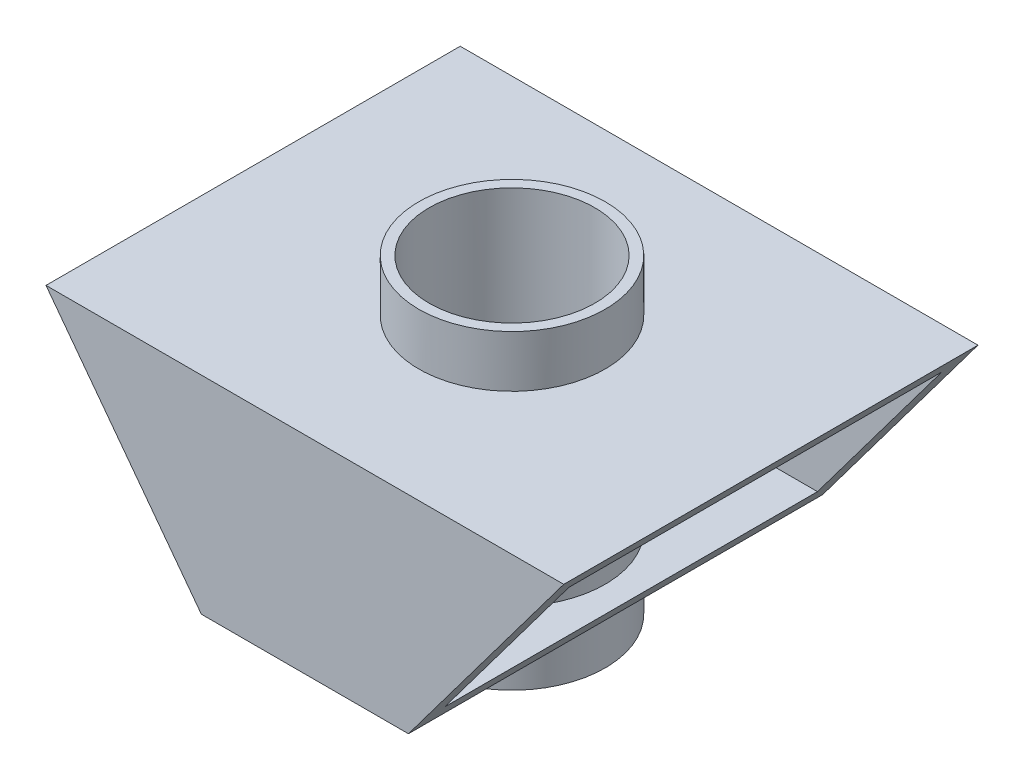
SolidWorks part; units mm, degrees
ref_plane "Front Plane" through (0, 0, 0) normal (0, 0, 1) x (1, 0, 0)
ref_plane "Top Plane" through (0, 0, 0) normal (0, 1, 0) x (1, 0, 0)
ref_plane "Right Plane" through (0, 0, 0) normal (1, 0, 0) x (0, 0, -1)
sketch "Sketch1" plane through (0, 0, 0) normal (0, 1, 0) x (1, 0, 0)
  line L0 (-25, 20) -> (25, -20) construction
  line L1 (-25, -20) -> (25, -20)
  line L2 (-25, -20) -> (-25, 20)
  line L3 (-25, 20) -> (25, 20)
  line L4 (25, -20) -> (25, 20)
  line L5 (25, 20) -> (-25, -20) construction
  point P5 (0, 0)
  point P6 (0, 0)
  point P7 (0.4418, 0.3526)
  point P8 (0, 0)
  dimension "D1" = 50
  dimension "D2" = 40
extrude "Boss-Extrude1" add sketch "Sketch1" along normal blind 20
sketch "Sketch2" plane through (25, 0, 0) normal (1, 0, 0) x (0, 0, -1)
  line L0 (18, 18) -> (-18, 18)
  line L5 (-18, 18) -> (-18, 2)
  line L6 (-18, 2) -> (18, 2)
  line L7 (18, 2) -> (18, 18)
  line L8 (-20, 0) -> (20, 0)
  line L9 (20, 0) -> (20, 20)
  line L10 (20, 20) -> (-20, 20)
  line L11 (-20, 20) -> (-20, 0)
  line L12 (-20, 0) -> (20, 0)
  line L13 (20, 0) -> (20, 20)
  line L14 (20, 20) -> (-20, 20)
  line L15 (-20, 20) -> (-20, 0)
  dimension "D1" = 0
  dimension "D2" = 2
extrude "Cut-Extrude1" cut sketch "Sketch2" against normal up to surface (50 mm away) contours L6 L7 L0 L5 region at (25, 10, 0) up to face at (-25, 10, 0)
sketch "Sketch3" plane through (0, 0, 20) normal (0, 0, 1) x (1, 0, 0)
  line L4 (-25, 0) -> (25, 0) construction
  line L5 (-25, 20) -> (-25, 0)
  line L6 (-25, 0) -> (-10, 0)
  line L7 (-10, 0) -> (-25, 20)
  line L8 (-25, 20) -> (25, 20) construction
  line L9 (-25, 20) -> (25, 20)
  line L10 (-25, 0) -> (25, 0)
  line L11 (0, 20) -> (0, 0) construction
  line L12 (25, 0) -> (10, 0)
  line L13 (25, 20) -> (25, 0)
  line L14 (10, 0) -> (25, 20)
  point P0 (-10, 0)
  line M8 (25, 0) -> (25, 20)
  dimension "D1" = 15
extrude "Cut-Extrude2" cut sketch "Sketch3" against normal up to surface (40 mm away) contours L14 L10 M8 | L7 L5 L6 region at (20, 6.6667, 20) up to face at (0, 10, -20)
sketch "Sketch5" plane through (0, 20, 0) normal (0, 1, 0) x (1, 0, 0)
  circle A0 centre (0, 0) radius 9
  point P2 (0, 0)
extrude "Boss-Extrude2" add sketch "Sketch5" along direction (0, -1, 0) on the side against the normal offset from surface 5 and the other way blind 5 up to face at (0, 0, 0) offset beyond the face yes
sketch "Sketch8" plane through (0, -5, 0) normal (0, -1, 0) x (-1, 0, 0)
  circle A0 centre (0, 0) radius 9
extrude "Boss-Extrude3" add sketch "Sketch8" against normal blind 19
sketch "Sketch9" plane through (0, 25, 0) normal (0, 1, 0) x (1, 0, 0)
  circle A0 centre (0, 0) radius 8
extrude "Cut-Extrude4" cut sketch "Sketch9" against normal up to surface (30 mm away) up to face at (0, -5, -9)
